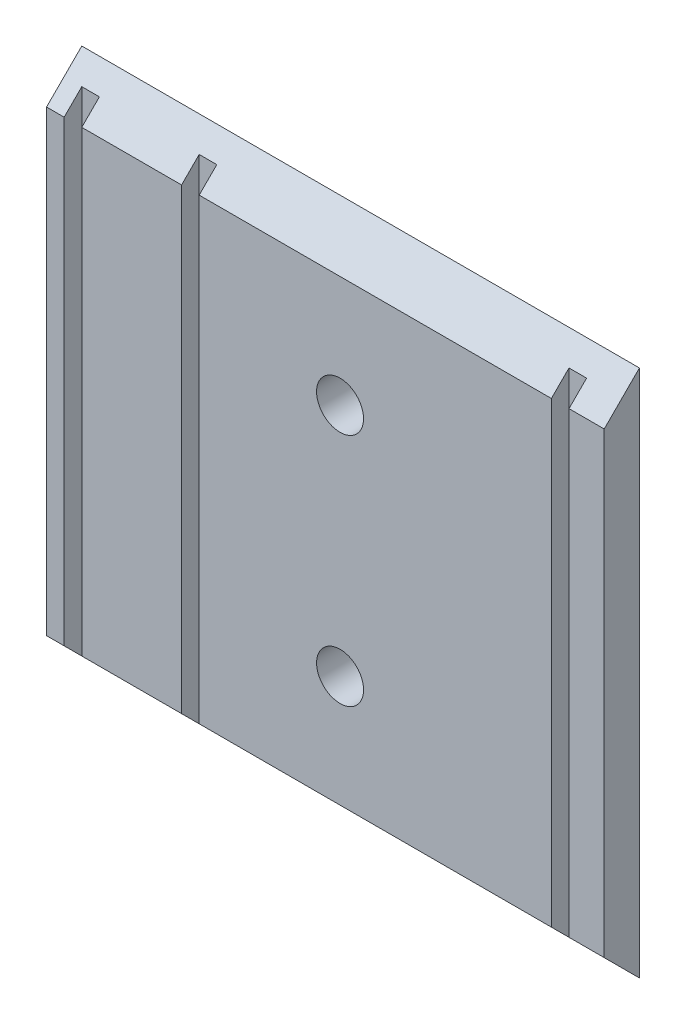
SolidWorks part; units mm, degrees
material "Maple"
ref_plane "Front Plane" through (0, 0, 0) normal (0, 0, 1) x (1, 0, 0)
ref_plane "Top Plane" through (0, 0, 0) normal (0, 1, 0) x (1, 0, 0)
ref_plane "Right Plane" through (0, 0, 0) normal (1, 0, 0) x (0, 0, -1)
sketch "Sketch1" plane through (0, 0, 0) normal (0, 0, 1) x (1, 0, 0)
  line L1 (-47.5, -45) -> (47.5, -45)
  line L2 (-47.5, -45) -> (-47.5, 45)
  line L3 (-47.5, 45) -> (47.5, 45)
  line L4 (47.5, -45) -> (47.5, 45)
  line L5 (-47.5, -45) -> (47.5, 45) construction
  line L6 (-47.5, 45) -> (47.5, -45) construction
  point P0 (0, 0)
  dimension "D1" = 95
  dimension "D2" = 90
extrude "Boss-Extrude1" add sketch "Sketch1" along normal blind 6
chamfer "Chamfer1" distance 6 angle 45 2 edges at (0, -45, 6) (0, 45, 6)
sketch "Sketch2" plane through (0, 0, 6) normal (0, 0, 1) x (1, 0, 0)
  line L0 (47.5, 45) -> (-47.5, 45) construction
  line L1 (-44.5, -45) -> (-41.5, -45)
  line L2 (-44.5, -45) -> (-44.5, 45)
  line L3 (-44.5, 45) -> (-41.5, 45)
  line L4 (-41.5, -45) -> (-41.5, 45)
  line L5 (-44.5, -45) -> (-41.5, 45) construction
  line L6 (-44.5, 45) -> (-41.5, -45) construction
  line L7 (-47.5, -45) -> (47.5, -45) construction
  line L8 (-47.5, 39) -> (-47.5, -39) construction
  point P0 (-43, 0)
  dimension "D1" = 3
  dimension "D2" = 3
extrude "Cut-Extrude1" cut sketch "Sketch2" against normal blind 3
pattern_linear "LPattern1" count 2 spacing 20 along (1, 0, 0) of "Cut-Extrude1"
sketch "Sketch3" plane through (0, 0, 0) normal (0, 0, -1) x (-1, 0, 0)
  line L0 (47.5, 45) -> (47.5, -45) construction
  circle A0 centre (-2.5, 20) radius 4
  dimension "D3" = 8
  dimension "D1" = 50
  dimension "D2" = 20
extrude "Cut-Extrude2" cut sketch "Sketch3" against normal through all
mirror "Mirror1" about plane through (0, 0, 0) normal (0, 1, 0) of "Cut-Extrude2"
sketch "Sketch4" plane through (0, 0, 6) normal (0, 0, 1) x (1, 0, 0)
  line L0 (47.5, 45) -> (-47.5, 45) construction
  line L1 (38.5, 45) -> (41.5, 45)
  line L2 (38.5, 45) -> (38.5, -45)
  line L3 (38.5, -45) -> (41.5, -45)
  line L4 (41.5, 45) -> (41.5, -45)
  line L5 (-47.5, -45) -> (47.5, -45) construction
  line L6 (47.5, -39) -> (47.5, 39) construction
  dimension "D1" = 3
  dimension "D2" = 9
extrude "Cut-Extrude3" cut sketch "Sketch4" against normal up to surface (3 mm away) up to face at (-43, 0, 3)
sketch "Sketch5" [suppressed] plane through (0, 0, 0) normal (0, 0, -1) x (-1, 0, 0)
  line L0 (45.5, 45) -> (45.5, -45) construction
  circle A0 centre (15.5, 28) radius 1.75
  dimension "D2" = 3.5
  dimension "D1" = 30
  dimension "D3" = 28
extrude "Cut-Extrude4" [suppressed] cut sketch "Sketch5" against normal through all
chamfer "Chamfer2" [suppressed] distance 2 angle 45
